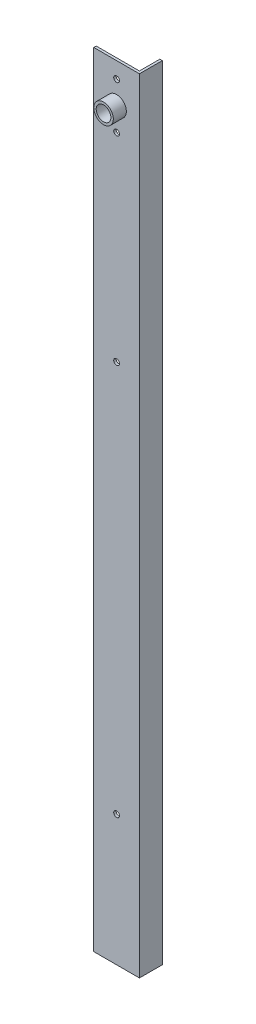
SolidWorks part; units mm, degrees
material "Galvanized Steel"
ref_plane "Front Plane" through (0, 0, 0) normal (0, 0, 1) x (1, 0, 0)
ref_plane "Top Plane" through (0, 0, 0) normal (0, 1, 0) x (1, 0, 0)
ref_plane "Right Plane" through (0, 0, 0) normal (1, 0, 0) x (0, 0, -1)
sketch "Sketch1" plane through (0, 0, 0) normal (0, 1, 0) x (1, 0, 0)
  line L1 (-44.45, -22.225) -> (44.45, -22.225)
  line L2 (-44.45, -22.225) -> (-44.45, 22.225)
  line L3 (-44.45, 22.225) -> (44.45, 22.225)
  line L4 (44.45, -22.225) -> (44.45, 22.225)
  line L5 (-44.45, -22.225) -> (44.45, 22.225) construction
  line L6 (-44.45, 22.225) -> (44.45, -22.225) construction
  point P0 (0, 0)
  dimension "D1" = 88.9
  dimension "D2" = 44.45
extrude "Boss-Extrude1" add sketch "Sketch1" along normal blind 1524
sketch "Sketch2" plane through (0, 0, 22.225) normal (0, 0, 1) x (1, 0, 0)
  line L0 (-44.45, 1524) -> (44.45, 1524) construction
  line L2 (0, 1402.7547) -> (0, 1492.8453) construction
  circle A0 centre (0, 1447.8) radius 7.9375
  circle A1 centre (0, 1492.8453) radius 5.588
  circle A2 centre (0, 1402.7547) radius 5.588
  point P5 (0, 1524)
  point P9 (0, 1447.8)
  dimension "D1" = 15.875
  dimension "D3" = 11.176
  dimension "D2" = 1447.8
  dimension "D4" = 90.0906
extrude "Cut-Extrude1" cut sketch "Sketch2" against normal up to next
sketch "Sketch4" plane through (0, 0, 22.225) normal (0, 0, 1) x (1, 0, 0)
  circle A0 centre (0, 1447.8) radius 14.2875
  circle A1 centre (0, 1447.8) radius 19.05
  dimension "D1" = 38.1
  dimension "D2" = 28.575
extrude "Boss-Extrude2" add sketch "Sketch4" along normal blind 25.4
sketch "Sketch5" plane through (0, 1524, 0) normal (0, 1, 0) x (1, 0, 0)
  line L8 (39.6875, 17.4625) -> (39.6875, 22.225)
  line L9 (44.45, 22.225) -> (-44.45, 22.225) construction
  line L10 (39.6875, 22.225) -> (-44.45, 22.225)
  line L11 (-44.45, 22.225) -> (-44.45, -17.4625)
  line L12 (39.6875, -17.4625) -> (39.6875, 17.4625)
  line L13 (39.6875, 17.4625) -> (-39.6875, 17.4625)
  line L14 (-39.6875, 17.4625) -> (-39.6875, -17.4625)
  line L15 (-39.6875, -17.4625) -> (39.6875, -17.4625)
  line L16 (39.6875, -17.4625) -> (39.6875, 17.4625)
  line L19 (-39.6875, -17.4625) -> (39.6875, -17.4625)
  line L20 (-44.45, 22.225) -> (-44.45, -22.225) construction
  line L21 (-44.45, -17.4625) -> (-39.6875, -17.4625)
  dimension "D1" = 4.7625
extrude "Cut-Extrude2" cut sketch "Sketch5" against normal up to next
sketch "Sketch6" plane through (0, 0, 0) normal (0, -1, 0) x (1, 0, 0)
  line L1 (44.45, -22.225) -> (-44.45, -22.225)
  line L2 (44.45, -22.225) -> (44.45, 22.225)
  line L3 (44.45, 22.225) -> (-44.45, 22.225)
  line L4 (-44.45, -22.225) -> (-44.45, 22.225)
extrude "Boss-Extrude3" add sketch "Sketch6" against normal blind 6.35
sketch "Sketch7" plane through (0, 0, 22.225) normal (0, 0, 1) x (1, 0, 0)
  line L0 (-44.45, 1524) -> (44.45, 1524) construction
  line L1 (-44.45, 0) -> (44.45, 0) construction
  circle A0 centre (0, 1016) radius 5.588
  circle A1 centre (0, 254) radius 5.588
  point P4 (0, 0)
  point P7 (0, 1524)
  dimension "D1" = 11.176
  dimension "D2" = 508
  dimension "D3" = 254
extrude "Cut-Extrude3" cut sketch "Sketch7" against normal through all
